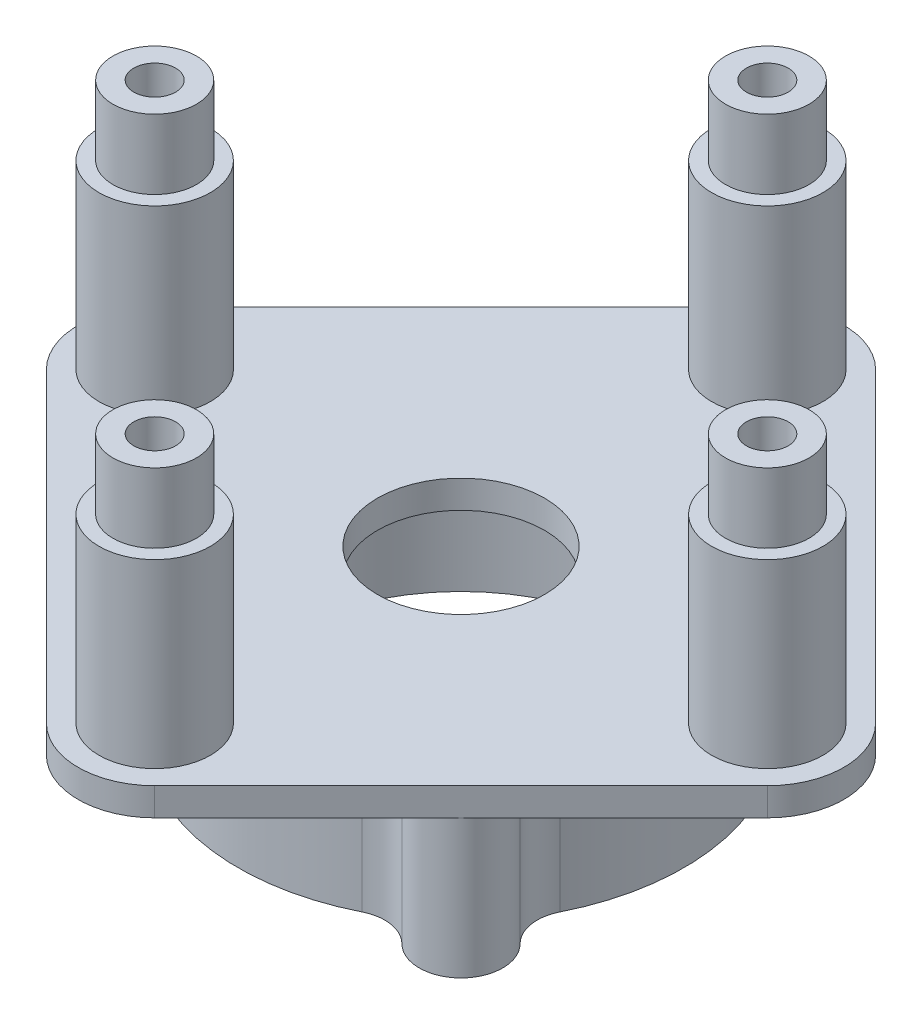
SolidWorks part; units mm, degrees
ref_plane "Front Plane" through (0, 0, 0) normal (0, 0, 1) x (1, 0, 0)
ref_plane "Top Plane" through (0, 0, 0) normal (0, 1, 0) x (1, 0, 0)
ref_plane "Right Plane" through (0, 0, 0) normal (1, 0, 0) x (0, 0, -1)
sketch "Sketch1" plane through (0, 0, 0) normal (0, 1, 0) x (1, 0, 0)
  line L0 (-7.5263, -6.3887) -> (-7.5627, -6.3887)
  line L1 (7.5627, -6.3887) -> (7.5263, -6.3887)
  line L2 (7.5263, -6.3887) -> (7.5263, 6.4316)
  line L3 (-7.5263, 6.4316) -> (-7.5263, -6.3887)
  line L4 (-9.1924, 9.1924) -> (-9.1924, -9.1924) construction
  line L5 (-9.1924, 9.1924) -> (9.1924, 9.1924) construction
  line L6 (-9.1924, -9.1924) -> (9.1924, -9.1924) construction
  line L7 (9.1924, 9.1924) -> (9.1924, -9.1924) construction
  line L8 (-9.1924, 9.1924) -> (9.1924, -9.1924) construction
  line L9 (-9.1924, -9.1924) -> (9.1924, 9.1924) construction
  arc A0 (-7.5627, -6.3887) -> (7.5627, -6.3887) centre (0, 0) ccw
  arc A1 (7.5263, 6.4316) -> (-7.5263, 6.4316) centre (0, 0) ccw
  circle A2 centre (0, 0) radius 15.9
  circle A3 centre (-9.1924, 9.1924) radius 1.5
  circle A4 centre (9.1924, 9.1924) radius 1.5
  circle A5 centre (9.1924, -9.1924) radius 1.5
  circle A6 centre (-9.1924, -9.1924) radius 1.5
  point P24 (0, 0)
  dimension "D1" = 31.8
  dimension "D3" = 9.9
  dimension "D6" = 3
  dimension "D2" = 12.8202
  dimension "D4" = 15.089
  dimension "D5" = 13
  dimension "D7" = 4
sketch "Sketch2" plane through (0, 0, 0) normal (0, 1, 0) x (1, 0, 0)
  line L0 (0, 0) -> (155.6578, 0) construction
  line L1 (-7.5263, 6.4316) -> (-7.5263, -6.3887) construction
  line L2 (-7.5263, -6.3887) -> (-7.5627, -6.3887) construction
  line L3 (7.5627, -6.3887) -> (7.5263, -6.3887) construction
  line L4 (7.5263, -6.3887) -> (7.5263, 6.4316) construction
  line L5 (-7.5263, 6.4316) -> (-7.5263, -6.3887)
  line L6 (-7.5263, -6.3887) -> (-7.5627, -6.3887)
  line L7 (7.5627, -6.3887) -> (7.5263, -6.3887)
  line L8 (7.5263, -6.3887) -> (7.5263, 6.4316)
  line L9 (-25.8891, -3.8891) -> (-3.8891, -25.8891)
  line L10 (-25.8891, 3.8891) -> (-3.8891, 25.8891)
  line L11 (3.8891, 25.8891) -> (25.8891, 3.8891)
  line L12 (25.8891, -3.8891) -> (3.8891, -25.8891)
  circle A0 centre (22, 0) radius 1.5
  circle A1 centre (22, 0) radius 4
  circle A2 centre (22, 0) radius 3
  circle A12 centre (22, 0) radius 5.5
  arc A13 (12.2869, 10.0916) -> (22, 5.5) centre (22, 18.0692) ccw
  arc A14 (12.2869, -10.0916) -> (22, -5.5) centre (22, -18.0692) cw
  circle A15 centre (0, 0) radius 15.9 construction
  circle A16 centre (0, 0) radius 15.9
  arc A17 (10.0916, -12.2869) -> (5.5, -22) centre (18.0692, -22) ccw
  circle A18 centre (0, -22) radius 5.5
  circle A19 centre (0, -22) radius 4
  circle A20 centre (0, -22) radius 3
  circle A21 centre (0, -22) radius 1.5
  arc A22 (-10.0916, -12.2869) -> (-5.5, -22) centre (-18.0692, -22) cw
  arc A23 (-12.2869, -10.0916) -> (-22, -5.5) centre (-22, -18.0692) ccw
  circle A24 centre (-22, 0) radius 5.5
  circle A25 centre (-22, 0) radius 4
  circle A26 centre (-22, 0) radius 3
  circle A27 centre (-22, 0) radius 1.5
  arc A28 (-12.2869, 10.0916) -> (-22, 5.5) centre (-22, 18.0692) cw
  arc A29 (-10.0916, 12.2869) -> (-5.5, 22) centre (-18.0692, 22) ccw
  circle A30 centre (0, 22) radius 5.5
  circle A31 centre (0, 22) radius 4
  circle A32 centre (0, 22) radius 3
  circle A33 centre (0, 22) radius 1.5
  arc A34 (10.0916, 12.2869) -> (5.5, 22) centre (18.0692, 22) cw
  arc A35 (-7.5627, -6.3887) -> (7.5627, -6.3887) centre (0, 0) ccw construction
  arc A36 (7.5263, 6.4316) -> (-7.5263, 6.4316) centre (0, 0) ccw construction
  circle A37 centre (9.1924, 9.1924) radius 1.5 construction
  circle A38 centre (9.1924, -9.1924) radius 1.5 construction
  circle A39 centre (-9.1924, -9.1924) radius 1.5 construction
  circle A40 centre (-9.1924, 9.1924) radius 1.5 construction
  arc A41 (-7.5627, -6.3887) -> (7.5627, -6.3887) centre (0, 0) ccw
  arc A42 (7.5263, 6.4316) -> (-7.5263, 6.4316) centre (0, 0) ccw
  circle A43 centre (9.1924, 9.1924) radius 1.5
  circle A44 centre (9.1924, -9.1924) radius 1.5
  circle A45 centre (-9.1924, -9.1924) radius 1.5
  circle A46 centre (-9.1924, 9.1924) radius 1.5
  point P19 (0, 0)
  point P54 (0, 0)
  point P79 (0, 0)
  dimension "D1" = 3
  dimension "D2" = 6
  dimension "D3" = 8
  dimension "D4" = 11
  dimension "D5" = 22
  dimension "D6" = 4
extrude "Boss-Extrude1" add sketch "Sketch2" along normal blind 2 contours A42 L8 A16 L7 A41 L6 L5 A46 A45 A44 A43 | A16 A22 A18 A17 | L0 A16 A14 A12 | A16 L0 A12 A13 | A12 L0 A1 | A1 L0 A2 | A2 L0 A0 | L0 A12 A1 | L0 A1 A2 | L0 A2 A0 | A18 A19 | A21 | A16 A34 A30 A29 | A30 A31 | A31 A32 | A32 A33 | A24 A25 | A25 A26 | A26 A27 | A16 A28 A24 A23 | L8 A42 L5 L6 A41 L7 | A46 | A43 | A44 | A45 | A24 L9 A18 A22 A16 A23 | A30 L10 A24 A28 A16 A29 | A34 A16 A13 A12 L11 A30 | A18 L12 A12 A14 A16 A17 | A19 region at (22, 0, -1.5671) region at (24.25, 0, 0.0671) region at (22, 0, -3.0894) region at (25.5, 0, 0.0894) region at (22, 0, -4.123) region at (26.75, 0, 0.123) region at (13.2937, 0, -13.2937) region at (13.2937, 0, 13.2937) region at (16.6203, 0, 4.8104) region at (16.6203, 0, -4.8104) region at (4.9376, 0, -24.0452) region at (0, 0, 27.3444) region at (0, 0, 0) region at (14.5461, 0, 5.2079) region at (6.5032, 0, -16.5324) region at (-13.2937, 0, -13.2937) region at (-13.2937, 0, 13.2937) region at (0, 0, 16.276) region at (-24.0452, 0, -4.9376) region at (-16.5324, 0, -6.5032) region at (0, 0, 22) region at (-25.8869, 0, 0) region at (-24.9151, 0, 0) region at (-3.8869, 0, -22) region at (-2.9151, 0, -22) region at (9.1924, 0, -9.1924) region at (9.1924, 0, 9.1924) region at (-9.1924, 0, 9.1924) region at (-9.1924, 0, -9.1924)
extrude "Boss-Extrude2" add sketch "Sketch2<4>" along normal blind 20 contours A19 A20 | A20 A21 | L0 A1 A2 | L0 A2 A0 | A2 L0 A0 | A1 L0 A2 | A31 A32 | A32 A33 | A25 A26 | A27 | A26 region at (22, 0, -1.5671) region at (24.25, 0, 0.0671) region at (22, 0, -3.0894) region at (25.5, 0, 0.0894) region at (-3.8869, 0, 22) region at (-2.9151, 0, 22) region at (-25.8869, 0, 0) region at (-22, 0, 0) region at (-3.8869, 0, -22) region at (-2.9151, 0, -22)
sketch "Sketch2<4>" plane through (0, 0, 0) normal (0, 1, 0) x (1, 0, 0) same geometry as "Sketch2"
extrude "Cut-Extrude1" cut sketch "Sketch2<5>" against normal blind 5 from surface contours A25 A26 | A31 A32 | A1 L0 A2 | L0 A1 A2 | A19 A20 region at (22, 0, -3.0894) region at (25.5, 0, 0.0894) region at (-3.8869, 0, 22) region at (-25.8869, 0, 0) region at (-3.8869, 0, -22) starting at face at (0, 20, 26)
sketch "Sketch2<5>" plane through (0, 0, 0) normal (0, 1, 0) x (1, 0, 0) same geometry as "Sketch2"
sketch "Sketch5" plane through (0, 0, 0) normal (0, -1, 0) x (1, 0, 0)
  line L0 (0, 0) -> (-12.7279, 0) construction
  point P2 (0, 0)
  circle B0 centre (0, 0) radius 60 construction
  circle B1 centre (0, 0) radius 6
  circle B2 centre (0, 0) radius 11
  circle B3 centre (0, 0) radius 13
  circle B4 centre (0, 0) radius 16
  circle B5 centre (12.7279, -12.7279) radius 1.5
  arc B6 (12.703, -9.728) -> (9.728, -12.703) centre (12.7279, -12.7279) cw
  arc B7 (-9.728, -12.703) -> (-12.703, -9.728) centre (-12.7279, -12.7279) cw
  circle B8 centre (-12.7279, -12.7279) radius 1.5
  arc B9 (-12.703, 9.728) -> (-9.728, 12.703) centre (-12.7279, 12.7279) cw
  circle B10 centre (-12.7279, 12.7279) radius 1.5
  arc B11 (9.728, 12.703) -> (12.703, 9.728) centre (12.7279, 12.7279) cw
  circle B12 centre (12.7279, 12.7279) radius 1.5
  arc B13 (-10.6066, 14.8492) -> (-7.1829, 14.297) centre (-8.5125, 16.9434) ccw
  arc B14 (-14.8492, 10.6066) -> (-14.297, 7.1829) centre (-16.9434, 8.5125) cw
  arc B15 (14.8492, 10.6066) -> (14.297, 7.1829) centre (16.9434, 8.5125) ccw
  arc B16 (10.6066, 14.8492) -> (7.1829, 14.297) centre (8.5125, 16.9434) cw
  arc B17 (10.6066, -14.8492) -> (7.1829, -14.297) centre (8.5125, -16.9434) ccw
  arc B18 (14.8492, -10.6066) -> (14.297, -7.1829) centre (16.9434, -8.5125) cw
  arc B19 (-14.8492, -10.6066) -> (-14.297, -7.1829) centre (-16.9434, -8.5125) ccw
  arc B20 (-10.6066, -14.8492) -> (-7.1829, -14.297) centre (-8.5125, -16.9434) cw
  dimension "D1" = 45
sketch_block_instance "Block2-1"
sketch_block "Block2" parameters "D1"=26, "D2"=22, "D3"=12, "D4"=3, "D5"=3, "D6"=18
extrude "Boss-Extrude3" add sketch "Sketch5" along normal blind 10 contours B4 B3 | B15 B11 B4 | B11 B4 B12 | B11 B16 B4 | B13 B9 B4 | B9 B14 B4 | B9 B4 B10 | B19 B7 B4 | B7 B4 B8 | B7 B20 B4 | B6 B18 B4 | B6 B4 B5 | B17 B6 B4 region at (15.1281, 0, -3.5866) region at (13.6886, 0, 9.2281) region at (13.6886, 0, -9.2281) region at (11.3737, 0, 11.3737) region at (13.8323, 0, -10.0301) region at (9.2281, 0, 13.6886) region at (9.2281, 0, -13.6886) region at (-9.2281, 0, 13.6886) region at (-9.2281, 0, -13.6886) region at (-11.3737, 0, 11.3737) region at (-10.0301, 0, -13.8323) region at (-13.6886, 0, 9.2281) region at (-13.6886, 0, -9.2281)
extrude "Boss-Extrude4" add sketch "Sketch5<3>" along normal blind 1 contours B3 B2 region at (-12.6323, 0, 0)
sketch "Sketch5<3>" plane through (0, 0, 0) normal (0, -1, 0) x (1, 0, 0) same geometry as "Sketch5"
extrude "Cut-Extrude2" cut sketch "Sketch5<4>" against normal blind 10 contours B1 region at (0, 0, 0)
sketch "Sketch5<4>" plane through (0, 0, 0) normal (0, -1, 0) x (1, 0, 0) same geometry as "Sketch5"
